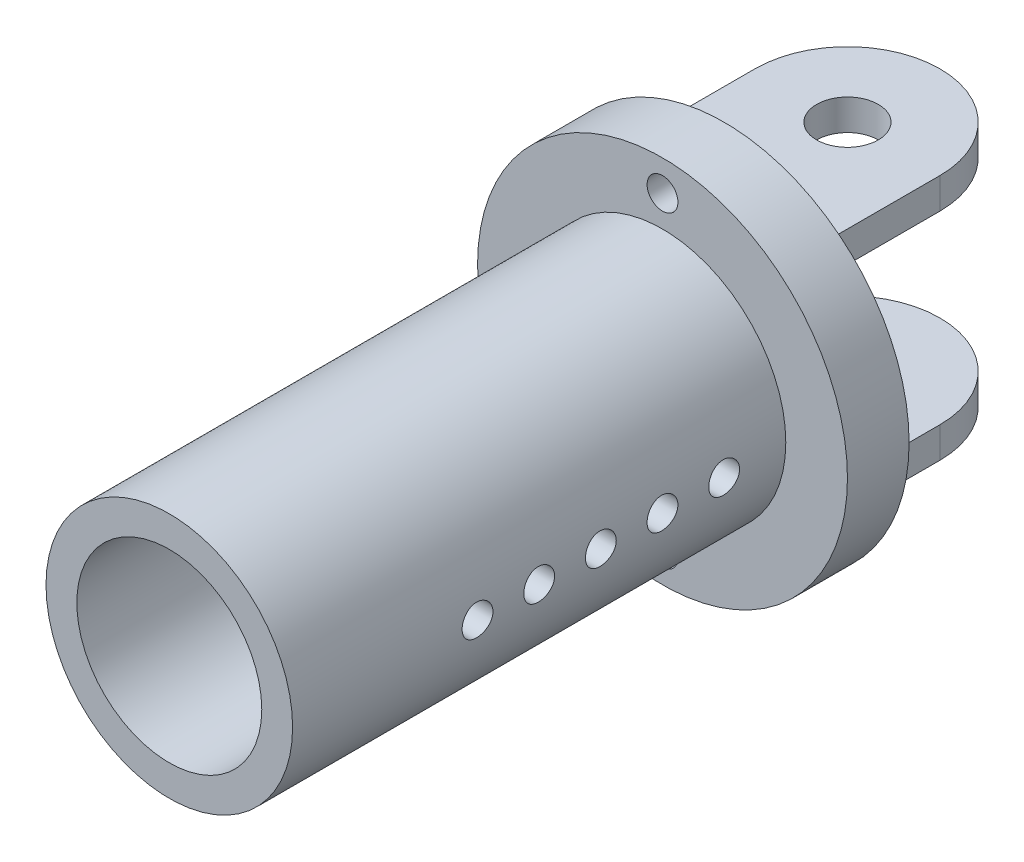
SolidWorks part; units mm, degrees
ref_plane "Front Plane" through (0, 0, 0) normal (0, 0, 1) x (1, 0, 0)
ref_plane "Top Plane" through (0, 0, 0) normal (0, 1, 0) x (1, 0, 0)
ref_plane "Right Plane" through (0, 0, 0) normal (1, 0, 0) x (0, 0, -1)
sketch "Sketch1" plane through (0, 0, 0) normal (0, 0, 1) x (1, 0, 0)
  circle A0 centre (0, 0) radius 19.05
  circle A1 centre (0, 0) radius 25.4
  circle A2 centre (0, 0) radius 38.1
  circle A3 centre (0, 0) radius 31.75 construction
  circle A4 centre (0, 31.75) radius 3.175
  circle A5 centre (0, -31.75) radius 3.175
  dimension "D1" = 76.2
  dimension "D2" = 50.8
  dimension "D3" = 38.1
  dimension "D4" = 63.5
  dimension "D5" = 6.35
extrude "Boss-Extrude1" add sketch "Sketch1" against normal blind 12.7 contours A2 A5 A4 A1 | A1 A0 region at (-24.6816, 0, 0) region at (-37.0224, 0, 0)
extrude "Boss-Extrude2" add sketch "Sketch1<3>" along normal blind 101.6 separate body contours A1 A0 region at (-24.6816, 0, 0)
sketch "Sketch1<3>" plane through (0, 0, 0) normal (0, 0, 1) x (1, 0, 0) same geometry as "Sketch1"
ref_plane "Plane1" through (0, 25.4, 0) normal (0, 1, 0) x (1, 0, 0)
sketch "Sketch2" plane through (0, 25.4, 0) normal (0, 1, 0) x (1, 0, 0)
  line L0 (19.05, 12.7) -> (19.05, 38.1)
  line L1 (25.4, -101.6) -> (25.4, 0) construction
  line L2 (-19.05, 38.1) -> (-19.05, 12.7)
  line L4 (3.175, 12.7) -> (-3.175, 12.7) construction
  line L5 (-19.05, 12.7) -> (19.05, 12.7)
  arc A0 (19.05, 38.1) -> (-19.05, 38.1) centre (0, 38.1) ccw
  circle A1 centre (0, 38.1) radius 6.35
  dimension "D2" = 38.1
  dimension "D3" = 12.7
  dimension "D1" = 25.4
extrude "Boss-Extrude3" add sketch "Sketch2" against normal blind 6.35
mirror "Mirror1" about plane through (0, 0, 0) normal (0, 1, 0) of "Boss-Extrude3"
sketch "Sketch3" plane through (0, 0, 0) normal (1, 0, 0) x (0, 0, -1)
  line L0 (0, 38.1) -> (0, -38.1) construction
  circle A0 centre (-63.5, 0) radius 3.175
  circle A1 centre (-50.8, 0) radius 3.175
  circle A2 centre (-38.1, 0) radius 3.175
  circle A3 centre (-25.4, 0) radius 3.175
  circle A4 centre (-12.7, 0) radius 3.175
  point P13 (0, 0)
  dimension "D3" = 6.35
  dimension "D2" = 12.7
  dimension "D4" = 50.8
  dimension "D1" = 5
extrude "Cut-Extrude1" cut sketch "Sketch3" against normal through all both and the other way through all
